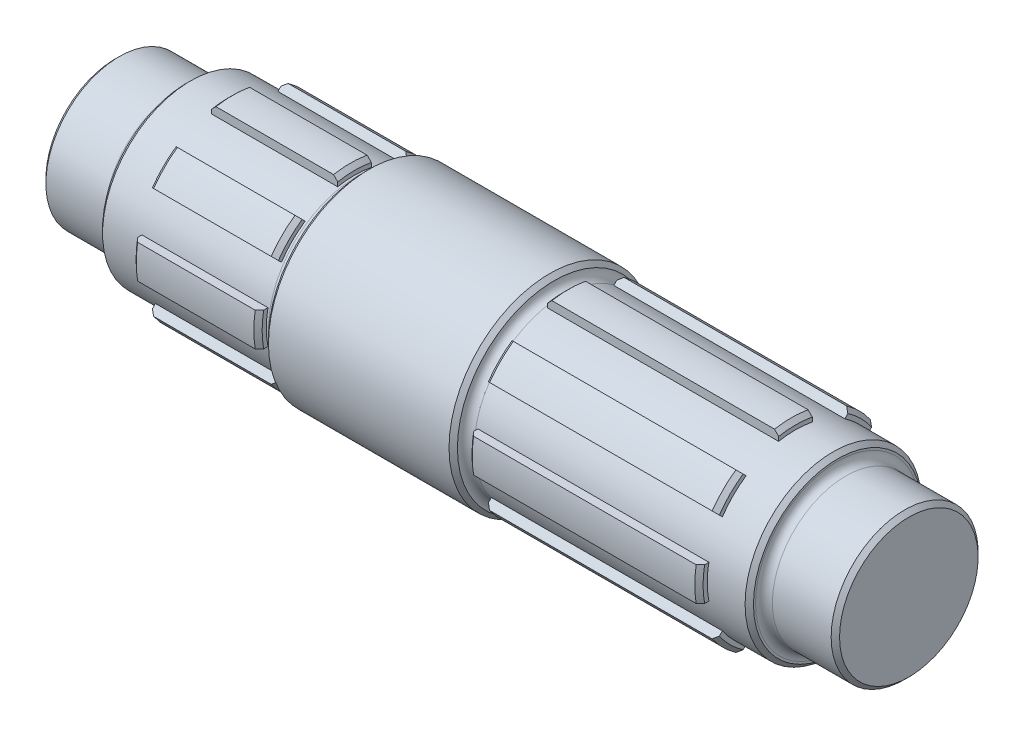
SolidWorks part; units mm, degrees
ref_plane "Front Plane" through (0, 0, 0) normal (0, 0, 1) x (1, 0, 0)
ref_plane "Top Plane" through (0, 0, 0) normal (0, 1, 0) x (1, 0, 0)
ref_plane "Right Plane" through (0, 0, 0) normal (1, 0, 0) x (0, 0, -1)
sketch "Sketch1" plane through (0, 0, 0) normal (0, 0, 1) x (1, 0, 0)
  line L0 (-127.9618, 0) -> (152.2611, 0) construction
  line L1 (-105, 0) -> (-105, 17.5)
  line L2 (-105, 17.5) -> (-88, 17.5)
  line L3 (-88, 17.5) -> (-88, 21)
  line L4 (-88, 21) -> (-78, 21)
  line L5 (-45.5, 21) -> (-45.5, 24)
  line L6 (-45.5, 24) -> (-0.5, 24)
  line L7 (-0.5, 24) -> (-0.5, 21)
  line L8 (-0.5, 21) -> (2, 21)
  line L9 (67, 21) -> (67, 17.5)
  line L10 (67, 17.5) -> (84, 17.5)
  line L11 (84, 17.5) -> (84, 0)
  line L12 (-78, 21) -> (-78, 23)
  line L13 (-78, 23) -> (-48, 23)
  line L14 (-48, 23) -> (-48, 21)
  line L15 (-48, 21) -> (-45.5, 21)
  line L16 (2, 21) -> (2, 23)
  line L17 (2, 23) -> (57, 23)
  line L18 (57, 23) -> (57, 21)
  line L19 (57, 21) -> (67, 21)
  line L20 (-105, 0) -> (84, 0)
  point P5 (-63, 21)
  point P18 (29.5, 21)
  dimension "D1" = 17.5
  dimension "D2" = 42
  dimension "D3" = 48
  dimension "D4" = 42
  dimension "D5" = 35
  dimension "D6" = 17
  dimension "D7" = 17
  dimension "D8" = 42.5
  dimension "D9" = 25
  dimension "D10" = 46
  dimension "D11" = 15
  dimension "D12" = 15
  dimension "D13" = 45
  dimension "D14" = 67.5
  dimension "D15" = 37.5
  dimension "D16" = 27.5
  dimension "D17" = 27.5
  dimension "D18" = 46
revolve "Revolve1" add sketch "Sketch1" angle 360 about L0
sketch "Sketch2" plane through (-78, 0, 0) normal (-1, 0, 0) x (0, 0, 1)
  line L0 (0, 0) -> (0, 32.0431) construction
  line L1 (-4, 22.6495) -> (-4, 20.6155)
  line L2 (4, 22.6495) -> (4, 20.6155)
  line L3 (13.1872, 18.844) -> (11.749, 17.4058)
  line L4 (18.844, 13.1872) -> (17.4058, 11.749)
  line L5 (22.6495, 4) -> (20.6155, 4)
  line L6 (22.6495, -4) -> (20.6155, -4)
  line L7 (18.844, -13.1872) -> (17.4058, -11.749)
  line L8 (13.1872, -18.844) -> (11.749, -17.4058)
  line L9 (4, -22.6495) -> (4, -20.6155)
  line L10 (-4, -22.6495) -> (-4, -20.6155)
  line L11 (-13.1872, -18.844) -> (-11.749, -17.4058)
  line L12 (-18.844, -13.1872) -> (-17.4058, -11.749)
  line L13 (-22.6495, -4) -> (-20.6155, -4)
  line L14 (-22.6495, 4) -> (-20.6155, 4)
  line L15 (-18.844, 13.1872) -> (-17.4058, 11.749)
  line L16 (-13.1872, 18.844) -> (-11.749, 17.4058)
  circle A0 centre (0, 0) radius 23 construction
  circle A1 centre (0, 0) radius 21 construction
  arc A2 (-4, 22.6495) -> (-13.1872, 18.844) centre (0, 0) ccw
  arc A3 (-4, 20.6155) -> (-11.749, 17.4058) centre (0, 0) ccw
  arc A4 (13.1872, 18.844) -> (4, 22.6495) centre (0, 0) ccw
  arc A5 (11.749, 17.4058) -> (4, 20.6155) centre (0, 0) ccw
  arc A6 (-18.844, 13.1872) -> (-22.6495, 4) centre (0, 0) ccw
  arc A7 (-17.4058, 11.749) -> (-20.6155, 4) centre (0, 0) ccw
  arc A8 (20.6155, 4) -> (17.4058, 11.749) centre (0, 0) ccw
  arc A9 (22.6495, 4) -> (18.844, 13.1872) centre (0, 0) ccw
  arc A10 (17.4058, -11.749) -> (20.6155, -4) centre (0, 0) ccw
  arc A11 (18.844, -13.1872) -> (22.6495, -4) centre (0, 0) ccw
  arc A12 (4, -20.6155) -> (11.749, -17.4058) centre (0, 0) ccw
  arc A13 (4, -22.6495) -> (13.1872, -18.844) centre (0, 0) ccw
  arc A14 (-11.749, -17.4058) -> (-4, -20.6155) centre (0, 0) ccw
  arc A15 (-13.1872, -18.844) -> (-4, -22.6495) centre (0, 0) ccw
  arc A16 (-22.6495, -4) -> (-18.844, -13.1872) centre (0, 0) ccw
  arc A17 (-20.6155, -4) -> (-17.4058, -11.749) centre (0, 0) ccw
  point P44 (0, 0)
  dimension "D1" = 4
  dimension "D2" = 8
extrude "Cut-Extrude1" cut sketch "Sketch2" against normal up to surface (30 mm away) up to face at (-48, 0, 23)
sketch "Sketch3" plane through (57, 0, 0) normal (1, 0, 0) x (0, 0, -1)
  line L2 (-11.749, -17.4058) -> (-13.1872, -18.844)
  line L3 (-4, -22.6495) -> (-4, -20.6155)
  line L4 (-11.749, -17.4058) -> (-13.1872, -18.844)
  line L5 (-4, -22.6495) -> (-4, -20.6155)
  line L6 (-20.6155, -4) -> (-22.6495, -4)
  line L7 (-18.844, -13.1872) -> (-17.4058, -11.749)
  line L8 (-20.6155, -4) -> (-22.6495, -4)
  line L9 (-18.844, -13.1872) -> (-17.4058, -11.749)
  line L10 (-17.4058, 11.749) -> (-18.844, 13.1872)
  line L11 (-22.6495, 4) -> (-20.6155, 4)
  line L12 (-17.4058, 11.749) -> (-18.844, 13.1872)
  line L13 (-22.6495, 4) -> (-20.6155, 4)
  line L14 (-13.1872, 18.844) -> (-11.749, 17.4058)
  line L15 (-4, 20.6155) -> (-4, 22.6495)
  line L16 (-13.1872, 18.844) -> (-11.749, 17.4058)
  line L17 (-4, 20.6155) -> (-4, 22.6495)
  line L18 (11.749, 17.4058) -> (13.1872, 18.844)
  line L19 (4, 22.6495) -> (4, 20.6155)
  line L20 (11.749, 17.4058) -> (13.1872, 18.844)
  line L21 (4, 22.6495) -> (4, 20.6155)
  line L22 (20.6155, 4) -> (22.6495, 4)
  line L23 (18.844, 13.1872) -> (17.4058, 11.749)
  line L24 (20.6155, 4) -> (22.6495, 4)
  line L25 (18.844, 13.1872) -> (17.4058, 11.749)
  line L26 (17.4058, -11.749) -> (18.844, -13.1872)
  line L27 (22.6495, -4) -> (20.6155, -4)
  line L28 (17.4058, -11.749) -> (18.844, -13.1872)
  line L29 (22.6495, -4) -> (20.6155, -4)
  line L30 (13.1872, -18.844) -> (11.749, -17.4058)
  line L31 (4, -20.6155) -> (4, -22.6495)
  line L32 (13.1872, -18.844) -> (11.749, -17.4058)
  line L33 (4, -20.6155) -> (4, -22.6495)
  arc A2 (-11.749, -17.4058) -> (-4, -20.6155) centre (0, 0) ccw
  arc A3 (-13.1872, -18.844) -> (-4, -22.6495) centre (0, 0) ccw
  arc A4 (-11.749, -17.4058) -> (-4, -20.6155) centre (0, 0) ccw
  arc A5 (-13.1872, -18.844) -> (-4, -22.6495) centre (0, 0) ccw
  arc A6 (-20.6155, -4) -> (-17.4058, -11.749) centre (0, 0) ccw
  arc A7 (-22.6495, -4) -> (-18.844, -13.1872) centre (0, 0) ccw
  arc A8 (-20.6155, -4) -> (-17.4058, -11.749) centre (0, 0) ccw
  arc A9 (-22.6495, -4) -> (-18.844, -13.1872) centre (0, 0) ccw
  arc A10 (-17.4058, 11.749) -> (-20.6155, 4) centre (0, 0) ccw
  arc A11 (-18.844, 13.1872) -> (-22.6495, 4) centre (0, 0) ccw
  arc A12 (-17.4058, 11.749) -> (-20.6155, 4) centre (0, 0) ccw
  arc A13 (-18.844, 13.1872) -> (-22.6495, 4) centre (0, 0) ccw
  arc A14 (-4, 20.6155) -> (-11.749, 17.4058) centre (0, 0) ccw
  arc A15 (-4, 22.6495) -> (-13.1872, 18.844) centre (0, 0) ccw
  arc A16 (-4, 20.6155) -> (-11.749, 17.4058) centre (0, 0) ccw
  arc A17 (-4, 22.6495) -> (-13.1872, 18.844) centre (0, 0) ccw
  arc A18 (11.749, 17.4058) -> (4, 20.6155) centre (0, 0) ccw
  arc A19 (13.1872, 18.844) -> (4, 22.6495) centre (0, 0) ccw
  arc A20 (11.749, 17.4058) -> (4, 20.6155) centre (0, 0) ccw
  arc A21 (13.1872, 18.844) -> (4, 22.6495) centre (0, 0) ccw
  arc A22 (20.6155, 4) -> (17.4058, 11.749) centre (0, 0) ccw
  arc A23 (22.6495, 4) -> (18.844, 13.1872) centre (0, 0) ccw
  arc A24 (20.6155, 4) -> (17.4058, 11.749) centre (0, 0) ccw
  arc A25 (22.6495, 4) -> (18.844, 13.1872) centre (0, 0) ccw
  arc A26 (17.4058, -11.749) -> (20.6155, -4) centre (0, 0) ccw
  arc A27 (18.844, -13.1872) -> (22.6495, -4) centre (0, 0) ccw
  arc A28 (17.4058, -11.749) -> (20.6155, -4) centre (0, 0) ccw
  arc A29 (18.844, -13.1872) -> (22.6495, -4) centre (0, 0) ccw
  arc A30 (4, -20.6155) -> (11.749, -17.4058) centre (0, 0) ccw
  arc A31 (4, -22.6495) -> (13.1872, -18.844) centre (0, 0) ccw
  arc A32 (4, -20.6155) -> (11.749, -17.4058) centre (0, 0) ccw
  arc A33 (4, -22.6495) -> (13.1872, -18.844) centre (0, 0) ccw
  dimension "D1" = 0
  dimension "D2" = 0
  dimension "D3" = 0
  dimension "D4" = 0
  dimension "D5" = 0
  dimension "D6" = 0
  dimension "D7" = 0
  dimension "D8" = 0
extrude "Cut-Extrude2" cut sketch "Sketch3" against normal up to surface (55 mm away) up to face at (2, 0, 21)
fillet "Fillet1" radius 2 4 edges at (-88, 0, 17.5) (-45.5, 0, 21) (-0.5, 0, 21) (67, 0, 17.5)
chamfer "Chamfer1" distance 1 angle 45 38 edges at (-48, -23, 0) (-78, -23, 0) (-78, -16.2635, -16.2635) (-48, -16.2635, -16.2635) (-78, 16.2635, 16.2635) (-78, 0, 23) (-78, -16.2635, 16.2635) (-48, -16.2635, 16.2635) (-48, 0, 23) (-48, 16.2635, 16.2635) (-48, 23, 0) (-78, 23, 0) (-78, 0, -23) (-48, 0, -23) (-48, 16.2635, -16.2635) (-78, 16.2635, -16.2635) (2, 23, 0) (2, 16.2635, -16.2635) (2, 0, -23) (2, -16.2635, -16.2635) (2, -23, 0) (2, -16.2635, 16.2635) (2, 0, 23) (2, 16.2635, 16.2635) (57, 0, 23) (57, 16.2635, 16.2635) (57, -16.2635, 16.2635) (57, -23, 0) (57, -16.2635, -16.2635) (57, 0, -23) (57, 16.2635, -16.2635) (-0.5, 0, 24) (57, 23, 0) (84, 0, 17.5) (67, 0, 21) (-45.5, 0, 24) (-88, 0, 21) (-105, 0, 17.5)
